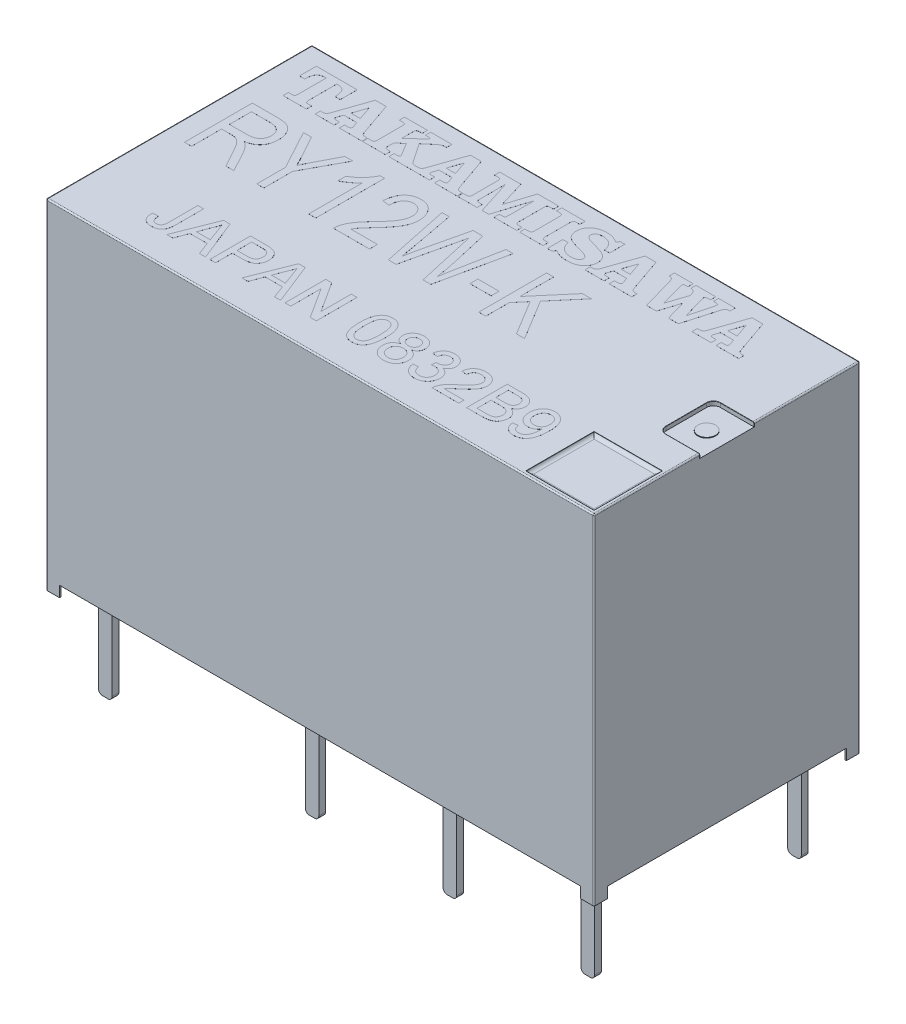
SolidWorks part; units mm, degrees
ref_plane "Спереди" through (0, 0, 0) normal (0, 0, 1) x (1, 0, 0)
ref_plane "Сверху" through (0, 0, 0) normal (0, 1, 0) x (1, 0, 0)
ref_plane "Справа" through (0, 0, 0) normal (1, 0, 0) x (0, 0, -1)
sketch "MainBody" plane through (0, 0, 0) normal (0, 1, 0) x (1, 0, 0)
  line L0 (-10.1, -4.9) -> (10.1, 4.9) construction
  line L1 (-10.1, 4.9) -> (10.1, 4.9)
  line L2 (-10.1, 4.9) -> (-10.1, -4.9)
  line L3 (-10.1, -4.9) -> (10.1, -4.9)
  line L4 (10.1, 4.9) -> (10.1, -4.9)
  line L5 (10.1, -4.9) -> (-10.1, 4.9) construction
  point P4 (0, 0)
  point P7 (-10.1, -4.9)
  dimension "D1" = 20.2
  dimension "D2" = 9.8
extrude "Бобышка-Вытянуть1" add sketch "MainBody" along normal blind 12.1
sketch "Supports" plane through (0, 0, 0) normal (0, 1, 0) x (1, 0, 0)
  line L0 (-10.1, -4.9) -> (-10.1, -4.4)
  line L1 (-10.1, 4.9) -> (-10.1, -4.9) construction
  line L2 (-10.1, -4.4) -> (-10.05, -4.4)
  line L3 (-10.1, -4.9) -> (10.1, -4.9) construction
  line L4 (-9.6, -4.9) -> (-10.1, -4.9)
  line L5 (-10.1, 4.4) -> (-10.05, 4.4)
  line L6 (-10.05, 4.4) -> (-9.6, 4.85)
  line L7 (-10.1, 4.9) -> (-10.1, 4.4)
  line L8 (-9.6, 4.85) -> (-9.6, 4.9)
  line L9 (10.1, 4.9) -> (-10.1, 4.9) construction
  line L10 (-9.6, 4.9) -> (-10.1, 4.9)
  line L11 (-10.05, -4.4) -> (-9.6, -4.85)
  line L12 (-9.6, -4.85) -> (-9.6, -4.9)
  line L13 (0, 8.8307) -> (0, -9.3662) construction
  line L14 (9.6, -4.85) -> (9.6, -4.9)
  line L15 (10.05, -4.4) -> (9.6, -4.85)
  line L16 (9.6, 4.9) -> (10.1, 4.9)
  line L17 (9.6, 4.85) -> (9.6, 4.9)
  line L18 (10.1, 4.9) -> (10.1, 4.4)
  line L19 (10.05, 4.4) -> (9.6, 4.85)
  line L20 (10.1, 4.4) -> (10.05, 4.4)
  line L21 (9.6, -4.9) -> (10.1, -4.9)
  line L22 (10.1, -4.4) -> (10.05, -4.4)
  line L23 (10.1, -4.9) -> (10.1, -4.4)
  dimension "D1" = 0.5
  dimension "D2" = 0.5
  dimension "D3" = 0.5
  dimension "D4" = 0.5
  dimension "D5" = 0.05
  dimension "D6" = 0.05
  dimension "D7" = 0.05
  dimension "D8" = 0.05
extrude "Бобышка-Вытянуть3" add sketch "Supports" against normal blind 0.4
fillet "Скругление4" radius 0.025 8 edges at (9.6, 0, -4.875) (10.075, 0, -4.4) (-9.6, 0, -4.875) (-10.075, 0, -4.4) (10.075, 0, 4.4) (9.6, 0, 4.875)
sketch "Hole" plane through (0, 12.1, 0) normal (0, 1, 0) x (1, 0, 0)
  line L0 (-10.1, -4.9) -> (10.1, -4.9) construction
  line L1 (9.95, -4.75) -> (7.45, -4.75)
  line L2 (9.95, -4.75) -> (9.95, -2.25)
  line L3 (9.95, -2.25) -> (7.45, -2.25)
  line L4 (7.45, -4.75) -> (7.45, -2.25)
  line L5 (10.1, -4.9) -> (10.1, 4.9) construction
  dimension "D1" = 0.15
  dimension "D2" = 0.15
  dimension "D3" = 2.5
  dimension "D4" = 2.5
extrude "Вырез-Вытянуть1" cut sketch "Hole" against normal blind 0.1
sketch "Notch" plane through (0, 12.1, 0) normal (0, 1, 0) x (1, 0, 0)
  line L0 (-12.605, 0) -> (29.805, 0) construction
  line L1 (10.1, -1) -> (10.1, 1)
  line L2 (10.1, -4.9) -> (10.1, 4.9) construction
  line L3 (10.1, 1) -> (8.85, 1)
  line L4 (10.1, -1) -> (8.85, -1)
  line L5 (8.6, 0.75) -> (8.6, -0.75)
  arc A0 (8.85, -1) -> (8.6, -0.75) centre (8.85, -0.75) cw
  arc A1 (8.6, 0.75) -> (8.85, 1) centre (8.85, 0.75) cw
  point P13 (8.6, 0)
  dimension "D1" = 1
  dimension "D4" = 0.25
  dimension "D2" = 2
  dimension "D3" = 1.5
extrude "Вырез-Вытянуть2" cut sketch "Notch" against normal blind 0.15
sketch "Point" plane through (0, 11.95, 0) normal (0, 1, 0) x (1, 0, 0)
  line L0 (14.3802, 0) -> (5.229, 0) construction
  line L1 (10.1, -1) -> (10.1, 1) construction
  circle A0 centre (9.35, 0) radius 0.325
  dimension "D1" = 0.65
  dimension "D2" = 0.75
extrude "Бобышка-Вытянуть4" add sketch "Point" along normal blind 0.025
fillet "Скругление5" radius 0.05 9 edges at (-10.1, 12.1, 0) (-10.1, 5.85, 4.9) (-10.1, 5.85, -4.9) (0, 12.1, -4.9) (0, 12.1, 4.9) (10.1, 12.1, -2.95) (10.1, 12.1, 2.95) (10.1, 5.85, -4.9) (10.1, 5.85, 4.9)
fillet "Скругление6" radius 0.01 9 edges at (8.6732, 12.1, -0.9268) (8.6, 12.1, 0) (8.6732, 12.1, 0.9268) (9.45, 12.1, 1) (10.0854, 12.0854, 1) (10.1, 12, 1) (9.45, 12.1, -1) (10.0854, 12.0854, -1) (10.1, 12, -1)
fillet "Скругление7" radius 0.01 4 edges at (9.95, 12.1, 3.5) (8.7, 12.1, 2.25) (8.7, 12.1, 4.75) (7.45, 12.1, 3.5)
sketch "Bottom" plane through (0, 0, 0) normal (0, -1, 0) x (1, 0, 0)
  line L0 (-10.075, 4.375) -> (-9.575, 4.875)
  line L1 (-9.575, 4.875) -> (9.575, 4.875)
  line L2 (9.575, 4.875) -> (10.075, 4.375)
  line L3 (10.075, 4.375) -> (10.075, -4.375)
  line L4 (10.075, -4.375) -> (9.575, -4.875)
  line L5 (9.575, -4.875) -> (-9.575, -4.875)
  line L6 (-9.575, -4.875) -> (-10.075, -4.375)
  line L7 (-10.075, -4.375) -> (-10.075, 4.375)
extrude "Вырез-Вытянуть3" cut sketch "Bottom" against normal blind 0.01
sketch "Pins" plane through (0, 0.01, 0) normal (0, -1, 0) x (1, 0, 0)
  line L0 (-9.13, 3.685) -> (-8.63, 3.935) construction
  line L1 (-9.13, 3.935) -> (-8.63, 3.935)
  line L2 (-9.13, 3.935) -> (-9.13, 3.685)
  line L3 (-9.13, 3.685) -> (-8.63, 3.685)
  line L4 (-8.63, 3.935) -> (-8.63, 3.685)
  line L5 (-8.63, 3.685) -> (-9.13, 3.935) construction
  line L6 (-1.51, 3.685) -> (-1.01, 3.935) construction
  line L7 (-1.51, 3.935) -> (-1.01, 3.935)
  line L8 (-1.51, 3.935) -> (-1.51, 3.685)
  line L9 (-1.51, 3.685) -> (-1.01, 3.685)
  line L10 (-1.01, 3.935) -> (-1.01, 3.685)
  line L11 (-1.01, 3.685) -> (-1.51, 3.935) construction
  line L12 (3.57, 3.685) -> (4.07, 3.935) construction
  line L13 (3.57, 3.935) -> (4.07, 3.935)
  line L14 (3.57, 3.935) -> (3.57, 3.685)
  line L15 (3.57, 3.685) -> (4.07, 3.685)
  line L16 (4.07, 3.935) -> (4.07, 3.685)
  line L17 (4.07, 3.685) -> (3.57, 3.935) construction
  line L18 (8.65, 3.685) -> (9.15, 3.935) construction
  line L19 (8.65, 3.935) -> (9.15, 3.935)
  line L20 (8.65, 3.935) -> (8.65, 3.685)
  line L21 (8.65, 3.685) -> (9.15, 3.685)
  line L22 (9.15, 3.935) -> (9.15, 3.685)
  line L23 (9.15, 3.685) -> (8.65, 3.935) construction
  line L24 (-17.3407, 0) -> (9.9262, 0) construction
  line L25 (9.15, -3.685) -> (8.65, -3.935) construction
  line L26 (8.65, -3.685) -> (9.15, -3.935) construction
  line L27 (4.07, -3.685) -> (3.57, -3.935) construction
  line L28 (3.57, -3.685) -> (4.07, -3.935) construction
  line L29 (-1.01, -3.685) -> (-1.51, -3.935) construction
  line L30 (-1.51, -3.685) -> (-1.01, -3.935) construction
  line L31 (-8.63, -3.685) -> (-9.13, -3.935) construction
  line L32 (-9.13, -3.685) -> (-8.63, -3.935) construction
  line L33 (9.15, -3.935) -> (9.15, -3.685)
  line L34 (8.65, -3.685) -> (9.15, -3.685)
  line L35 (8.65, -3.935) -> (8.65, -3.685)
  line L36 (8.65, -3.935) -> (9.15, -3.935)
  line L37 (4.07, -3.935) -> (4.07, -3.685)
  line L38 (3.57, -3.685) -> (4.07, -3.685)
  line L39 (3.57, -3.935) -> (3.57, -3.685)
  line L40 (3.57, -3.935) -> (4.07, -3.935)
  line L41 (-1.01, -3.935) -> (-1.01, -3.685)
  line L42 (-1.51, -3.685) -> (-1.01, -3.685)
  line L43 (-1.51, -3.935) -> (-1.51, -3.685)
  line L44 (-1.51, -3.935) -> (-1.01, -3.935)
  line L45 (-8.63, -3.935) -> (-8.63, -3.685)
  line L46 (-9.13, -3.685) -> (-8.63, -3.685)
  line L47 (-9.13, -3.935) -> (-9.13, -3.685)
  line L48 (-9.13, -3.935) -> (-8.63, -3.935)
  line L49 (-10.1, -4.375) -> (-10.1, 4.375) construction
  point P4 (-8.88, 3.81)
  point P9 (-1.26, 3.81)
  point P14 (3.82, 3.81)
  point P19 (8.9, 3.81)
  point P38 (8.9, -3.81)
  point P39 (3.82, -3.81)
  point P40 (-1.26, -3.81)
  point P41 (-8.88, -3.81)
  dimension "D1" = 0.5
  dimension "D2" = 0.25
  dimension "D3" = 3.81
  dimension "D4" = 7.62
  dimension "D5" = 5.08
  dimension "D6" = 5.08
  dimension "D7" = 1.22
extrude "Бобышка-Вытянуть7" add sketch "Pins" along normal blind 3.71
fillet "Скругление13" radius 0.025 32 edges at (-8.63, 0.01, -3.81) (-8.88, 0.01, -3.685) (-8.88, 0.01, -3.935) (-9.13, 0.01, -3.81) (-8.63, 0.01, 3.81) (-8.88, 0.01, 3.685) (-8.88, 0.01, 3.935) (-9.13, 0.01, 3.81) (-1.01, 0.01, 3.81) (-1.26, 0.01, 3.685) (-1.26, 0.01, 3.935) (-1.51, 0.01, 3.81) (4.07, 0.01, 3.81) (3.82, 0.01, 3.935) (3.82, 0.01, 3.685) (3.57, 0.01, 3.81) (8.9, 0.01, 3.685) (8.65, 0.01, 3.81) (8.9, 0.01, 3.935) (9.15, 0.01, 3.81) (9.15, 0.01, -3.81) (8.9, 0.01, -3.685) (8.9, 0.01, -3.935) (8.65, 0.01, -3.81) (3.57, 0.01, -3.81) (3.82, 0.01, -3.935) (4.07, 0.01, -3.81) (3.82, 0.01, -3.685) (-1.01, 0.01, -3.81) (-1.26, 0.01, -3.685) (-1.26, 0.01, -3.935) (-1.51, 0.01, -3.81)
fillet "Скругление14" radius 0.15 16 edges at (-8.63, -3.7, 3.81) (-9.13, -3.7, 3.81) (-8.63, -3.7, -3.81) (-9.13, -3.7, -3.81) (-1.51, -3.7, -3.81) (-1.01, -3.7, -3.81) (3.57, -3.7, -3.81) (4.07, -3.7, -3.81) (8.65, -3.7, -3.81) (9.15, -3.7, -3.81) (9.15, -3.7, 3.81) (8.65, -3.7, 3.81) (4.07, -3.7, 3.81) (3.57, -3.7, 3.81) (-1.01, -3.7, 3.81) (-1.51, -3.7, 3.81)
sketch "TextName" plane through (0, 12.1, 0) normal (0, 1, 0) x (1, 0, 0)
  text T0 "TAKAMISAWA" font "Clarendon Hv BT" height 1.55
sketch "TextModel" plane through (0, 12.1, 0) normal (0, 1, 0) x (1, 0, 0)
  text T0 "RY12W-K" font "Arial Narrow" height 2.5
sketch "TextN" plane through (0, 12.1, 0) normal (0, 1, 0) x (1, 0, 0)
  text T0 "JAPAN 0832B9" font "Arial" height 1.5
extrude "Бобышка-Вытянуть8" add sketch "TextName" along normal blind 0.001
extrude "Бобышка-Вытянуть9" add sketch "TextModel" along normal blind 0.001
extrude "Бобышка-Вытянуть10" add sketch "TextN" along normal blind 0.001
fillet "Скругление15" radius 0.15 4 edges at (9.95, 12, 3.5) (8.7, 12, 4.75) (8.7, 12, 2.25) (7.45, 12, 3.5)
